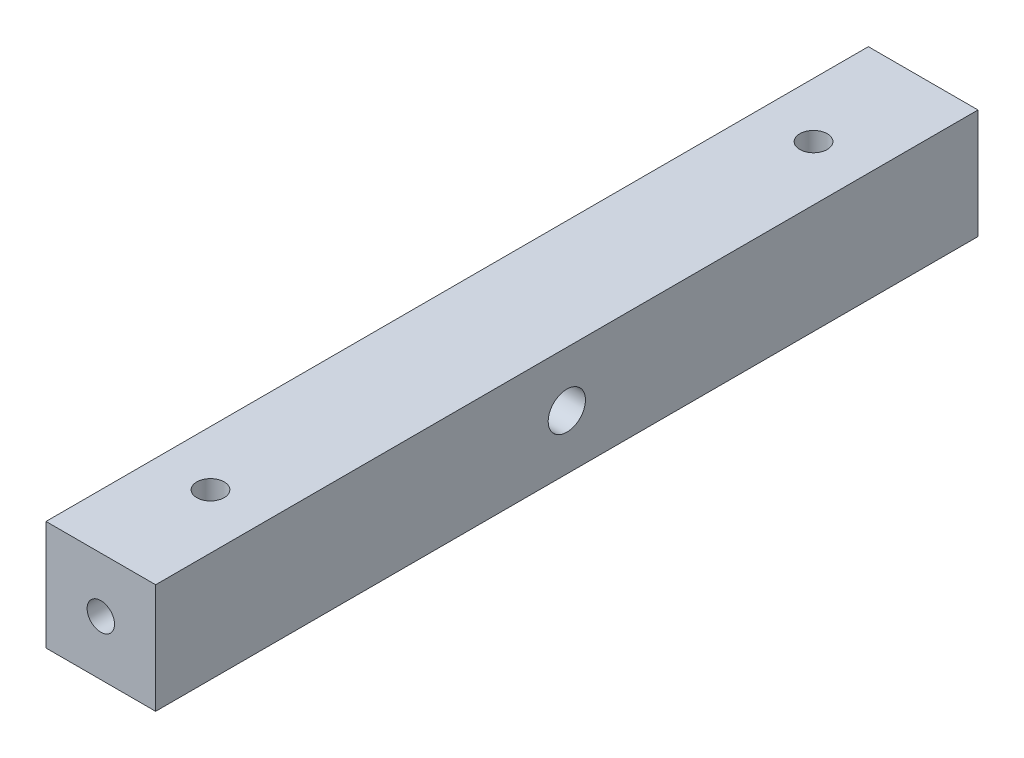
SolidWorks part; units mm, degrees
material "1060 Alloy"
ref_plane "Front Plane" through (0, 0, 0) normal (0, 0, 1) x (1, 0, 0)
ref_plane "Top Plane" through (0, 0, 0) normal (0, 1, 0) x (1, 0, 0)
ref_plane "Right Plane" through (0, 0, 0) normal (1, 0, 0) x (0, 0, -1)
sketch "Sketch1" plane through (0, 0, 0) normal (0, 0, 1) x (1, 0, 0)
  line L1 (37.5, -37.5) -> (27.5, -37.5)
  line L2 (37.5, -37.5) -> (37.5, -27.5)
  line L3 (37.5, -27.5) -> (27.5, -27.5)
  line L4 (27.5, -37.5) -> (27.5, -27.5)
  line L5 (37.5, -37.5) -> (27.5, -27.5) construction
  line L6 (37.5, -27.5) -> (27.5, -37.5) construction
  point P0 (32.5, -32.5)
  dimension "D1" = 5
extrude "Boss-Extrude1" add sketch "Sketch1" along normal up to surface (75 mm away)
hole_wizard "M3x0.5 Tapped Hole1" positions "Sketch3" profile "Sketch2" tap size "M3x0.5" standard "Ansi Metric"
sketch "Sketch3" plane through (0, 0, 75) normal (0, 0, 1) x (1, 0, 0)
  point P3 (32.5, -32.5)
sketch "Sketch2" plane through (32.5, -32.5, 75) normal (1, 0, 0) x (0, -1, 0)
  line L0 (0, 0) -> (0, 8.2511)
  line L1 (0, 8.2511) -> (1.25, 7.5)
  line L2 (1.25, 7.5) -> (1.25, 0)
  line L5 (1.25, 0) -> (0, 0)
  line L10 (0, 8.2511) -> (-1.25, 7.5) construction
  line L11 (0, -6.35) -> (0, 107.95) construction
  dimension "Tap Drill Dia." = 2.5
  dimension "Tap Drill Depth" = 7.5
  dimension "Drill Angle" = 118
cosmetic thread "Hole Thread1" parameters "D1"=6, "D2"=3
hole_wizard "M3x0.5 Tapped Hole2" positions "Sketch5" profile "Sketch4" tap size "M3x0.5" standard "Ansi Metric"
sketch "Sketch5" plane through (0, 0, 0) normal (0, 0, -1) x (-1, 0, 0)
  point P3 (-32.5, -32.5)
sketch "Sketch4" plane through (32.5, -32.5, 0) normal (1, 0, 0) x (0, 1, 0)
  line L0 (0, 0) -> (0, 8.2511)
  line L1 (0, 8.2511) -> (1.25, 7.5)
  line L2 (1.25, 7.5) -> (1.25, 0)
  line L5 (1.25, 0) -> (0, 0)
  line L10 (0, 8.2511) -> (-1.25, 7.5) construction
  line L11 (0, -6.35) -> (0, 107.95) construction
  dimension "Tap Drill Dia." = 2.5
  dimension "Tap Drill Depth" = 7.5
  dimension "Drill Angle" = 118
cosmetic thread "Hole Thread2" parameters "D1"=6, "D2"=3
hole_wizard "CSK for M3 Oval Head Machine Screw1" positions "3DSketch1" profile "Sketch6" countersink size "M3" standard "Ansi Metric" end condition through all
sketch3d "3DSketch1"
  line L0 (27.5, -32.5, 0) -> (27.5, -32.5, 75) construction
  line L1 (27.5, -27.5, 0) -> (27.5, -37.5, 0) construction
  line L2 (27.5, -27.5, 75) -> (27.5, -37.5, 75) construction
  point P0 (27.5, -32.5, 37.5)
sketch "Sketch6" plane through (27.5, -32.5, 37.5) normal (0, 1, 0) x (0, 0, 1)
  line L0 (0, 0) -> (0, 10)
  line L1 (0, 10) -> (1.7, 10)
  line L2 (1.7, 10) -> (1.7, 1.45)
  line L3 (1.7, 1.45) -> (3.15, 0)
  line L5 (3.15, 0) -> (0, 0)
  line L6 (-1.7, 1.45) -> (-3.15, 0) construction
  line L11 (0, -6.35) -> (0, 107.95) construction
  dimension "Thru Hole Dia." = 3.4
  dimension "Thru Hole Depth" = 10
  dimension "Near C'Sink Dia." = 6.3
  dimension "Near C'Sink Angle" = 90
hole_wizard "M3x0.5 Tapped Hole3" positions "Sketch8" profile "Sketch7" tap size "M3x0.5" standard "Ansi Metric" end condition up to next
sketch "Sketch8" plane through (0, -27.5, 0) normal (0, 1, 0) x (-1, 0, 0)
  point P1 (-32.5, 65)
  point P5 (-32.5, 10)
cosmetic thread "Hole Thread3" parameters "D2"=3
cosmetic thread "Hole Thread4" parameters "D2"=3
sketch "Sketch7" plane through (32.5, -27.5, 65) normal (1, 0, 0) x (0, 0, 1)
  line L0 (0, 0) -> (0, 10)
  line L1 (0, 10) -> (1.25, 10)
  line L2 (1.25, 10) -> (1.25, 0)
  line L5 (1.25, 0) -> (0, 0)
  line L11 (0, -6.35) -> (0, 107.95) construction
  dimension "Thru Tap Drill Dia." = 2.5
  dimension "Thru Tap Drill Depth" = 10
